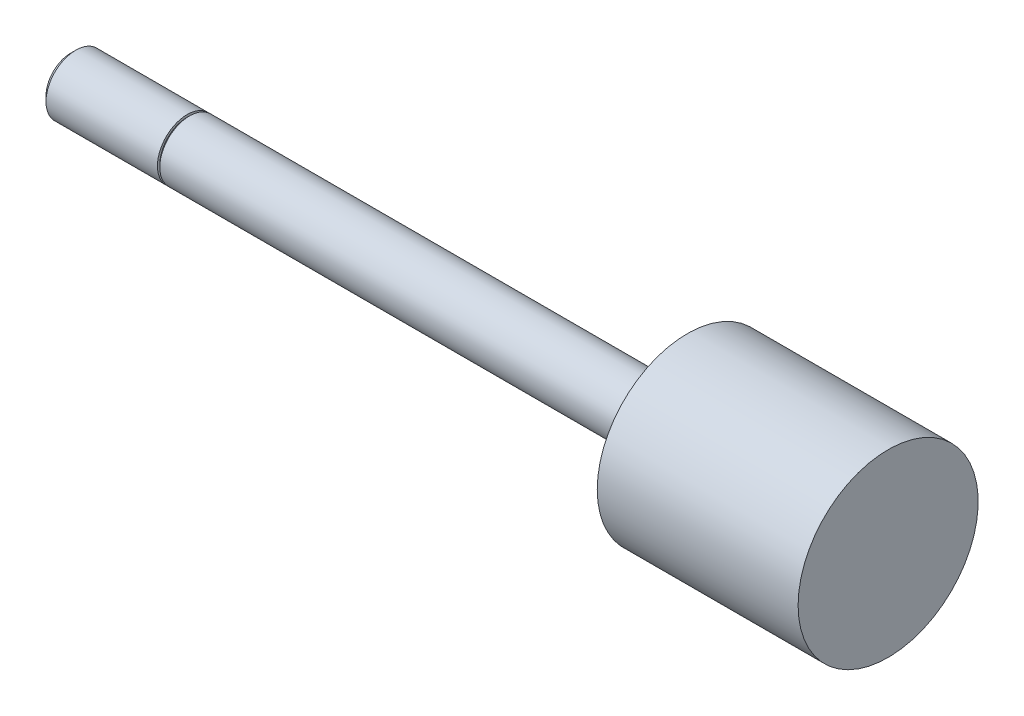
SolidWorks part; units mm, degrees
material "Plain Carbon Steel"
ref_plane "Front Plane" through (0, 0, 0) normal (0, 0, 1) x (1, 0, 0)
ref_plane "Top Plane" through (0, 0, 0) normal (0, 1, 0) x (1, 0, 0)
ref_plane "Right Plane" through (0, 0, 0) normal (1, 0, 0) x (0, 0, -1)
sketch "Sketch1" plane through (0, 0, 0) normal (0, 0, 1) x (1, 0, 0)
  line L0 (0, 0) -> (0, 3.175)
  line L1 (0, 3.175) -> (53.1876, 3.175)
  line L2 (53.1876, 3.175) -> (53.1876, 9.6203)
  line L3 (53.1876, 9.6203) -> (74.6506, 9.6203)
  line L4 (74.6506, 9.6203) -> (74.6506, 0)
  line L5 (74.6506, 0) -> (0, 0)
  line L6 (74.6506, 0) -> (0, 0) construction
revolve "Revolve1" add sketch "Sketch1" angle 360 about L6 reverse direction yes
cosmetic thread "Cosmetic Thread1" parameters "D1"=12.7, "D2"=5.268
sketch "Sketch2" plane through (0, 0, 0) normal (0, 0, 1) x (1, 0, 0)
  line L0 (-12.7, 0) -> (-12.7, 2.634)
  line L1 (-12.7, 2.634) -> (-12.159, 3.175)
  line L2 (-12.159, 3.175) -> (0, 3.175)
  line L3 (0, 3.175) -> (0, 0)
  line L4 (0, 0) -> (-12.7, 0)
  line L5 (0, 0) -> (-12.7, 0) construction
revolve "Revolve2" add sketch "Sketch2" angle 360 about L5 reverse direction yes
ref_plane "Plane1" through (0, 0, 0) normal (1, 0, 0) x (0, 0, -1)
ref_plane "Plane2" through (0, 0, 0) normal (1, 0, 0) x (0, 0, -1)
ref_plane "Plane3" through (127.8382, 0, 0) normal (1, 0, 0) x (0, 0, -1)
ref_plane "Plane4" through (-12.7, 0, 0) normal (1, 0, 0) x (0, 0, -1)
sketch "Sketch3" plane through (0, 0, 0) normal (0, 0, 1) x (1, 0, 0)
  line L0 (-0.254, 2.921) -> (0, 2.921)
  line L1 (0, 2.921) -> (0, 3.429)
  line L2 (0, 3.429) -> (-0.254, 3.429)
  line L3 (-0.254, 3.429) -> (-0.254, 2.921)
  line L4 (0, 0) -> (-0.254, 0) construction
revolve "Cut-Revolve1" cut sketch "Sketch3" angle 360 about L4 reverse direction yes
ref_plane "Plane5" through (0, 0, 0) normal (1, 0, 0) x (0, 0, -1)
ref_plane "Plane6" through (0, 0, 0) normal (1, 0, 0) x (0, 0, -1)
ref_plane "Plane7" through (-16.764, 0, 0) normal (1, 0, 0) x (0, 0, -1)
ref_plane "dia1 XY" through (0, 0, 0) normal (1, 0, 0) x (0, 0, -1)
ref_plane "dia1 XZ" through (0, 3.175, 0) normal (0, -1, 0) x (-1, 0, 0)
ref_plane "dia1 YZ" through (0, 0, 0) normal (0, 0, -1) x (-1, 0, 0)
ref_axis "dia1 X" through (0, 3.175, 80.9) along (0, 0, -1)
ref_axis "dia1 Y" through (0, -50, 0) along (0, 1, 0)
ref_axis "dia1 Z" through (80.9, 3.175, 0) along (-1, 0, 0)
sketch3d "dia1"
  point P0 (0, 3.175, 0)
ref_plane "dia12 XY" through (0, 0, 0) normal (1, 0, 0) x (0, 0, -1)
ref_plane "dia12 XZ" through (0, 0, 0) normal (0, -1, 0) x (-1, 0, 0)
ref_plane "dia12 YZ" through (0, 0, 10.9537) normal (0, 0, -1) x (-1, 0, 0)
ref_axis "dia12 X" through (0, 0, 80.9) along (0, 0, -1)
ref_axis "dia12 Y" through (0, -50, 10.9537) along (0, 1, 0)
ref_axis "dia12 Z" through (80.9, 0, 10.9537) along (-1, 0, 0)
sketch3d "dia12"
  point P0 (0, 0, 10.9537)
ref_plane "dia1r XY" through (0, 0, 0) normal (1, 0, 0) x (0, 0, -1)
ref_plane "dia1r XZ" through (0, 0, 0) normal (0, -1, 0) x (-1, 0, 0)
ref_plane "dia1r YZ" through (0, 0, 10.2235) normal (0, 0, -1) x (-1, 0, 0)
ref_axis "dia1r X" through (0, 0, 80.9) along (0, 0, -1)
ref_axis "dia1r Y" through (0, -50, 10.2235) along (0, 1, 0)
ref_axis "dia1r Z" through (80.9, 0, 10.2235) along (-1, 0, 0)
sketch3d "dia1r"
  point P0 (0, 0, 10.2235)
ref_plane "dia2 XY" through (0, 0, 0) normal (1, 0, 0) x (0, 0, -1)
ref_plane "dia2 XZ" through (0, -3.175, 0) normal (0, -1, 0) x (-1, 0, 0)
ref_plane "dia2 YZ" through (0, 0, 0) normal (0, 0, -1) x (-1, 0, 0)
ref_axis "dia2 X" through (0, -3.175, 80.9) along (0, 0, -1)
ref_axis "dia2 Y" through (0, -50, 0) along (0, 1, 0)
ref_axis "dia2 Z" through (80.9, -3.175, 0) along (-1, 0, 0)
sketch3d "dia2"
  point P0 (0, -3.175, 0)
ref_plane "dia22 XY" through (0, 0, 0) normal (1, 0, 0) x (0, 0, -1)
ref_plane "dia22 XZ" through (0, 0, 0) normal (0, -1, 0) x (-1, 0, 0)
ref_plane "dia22 YZ" through (0, 0, -10.9537) normal (0, 0, -1) x (-1, 0, 0)
ref_axis "dia22 X" through (0, 0, 80.9) along (0, 0, -1)
ref_axis "dia22 Y" through (0, -50, -10.9537) along (0, 1, 0)
ref_axis "dia22 Z" through (80.9, 0, -10.9537) along (-1, 0, 0)
sketch3d "dia22"
  point P0 (0, 0, -10.9537)
ref_plane "dia2r XY" through (0, 0, 0) normal (1, 0, 0) x (0, 0, -1)
ref_plane "dia2r XZ" through (0, 0, 0) normal (0, -1, 0) x (-1, 0, 0)
ref_plane "dia2r YZ" through (0, 0, -10.2235) normal (0, 0, -1) x (-1, 0, 0)
ref_axis "dia2r X" through (0, 0, 80.9) along (0, 0, -1)
ref_axis "dia2r Y" through (0, -50, -10.2235) along (0, 1, 0)
ref_axis "dia2r Z" through (80.9, 0, -10.2235) along (-1, 0, 0)
sketch3d "dia2r"
  point P0 (0, 0, -10.2235)
ref_plane "rl1 XY" through (-12.7, 0, 0) normal (1, 0, 0) x (0, 0, -1)
ref_plane "rl1 XZ" through (0, 0, 0) normal (0, -1, 0) x (-1, 0, 0)
ref_plane "rl1 YZ" through (0, 0, 0) normal (0, 0, -1) x (-1, 0, 0)
ref_axis "rl1 X" through (-12.7, 0, 80.9) along (0, 0, -1)
ref_axis "rl1 Y" through (-12.7, -50, 0) along (0, 1, 0)
ref_axis "rl1 Z" through (80.9, 0, 0) along (-1, 0, 0)
sketch3d "rl1"
  point P0 (-12.7, 0, 0)
ref_plane "rl2 XY" through (0, 0, 0) normal (1, 0, 0) x (0, 0, -1)
ref_plane "rl2 XZ" through (0, 0, 0) normal (0, -1, 0) x (-1, 0, 0)
ref_plane "rl2 YZ" through (0, 0, 0) normal (0, 0, -1) x (-1, 0, 0)
ref_axis "rl2 X" through (0, 0, 80.9) along (0, 0, -1)
ref_axis "rl2 Y" through (0, -50, 0) along (0, 1, 0)
ref_axis "rl2 Z" through (80.9, 0, 0) along (-1, 0, 0)
sketch3d "rl2"
  point P0 (0, 0, 0)
ref_plane "rod_cp XY" through (0, 0, 0) normal (1, 0, 0) x (0, 0, -1)
ref_plane "rod_cp XZ" through (0, 0, 0) normal (0, -1, 0) x (-1, 0, 0)
ref_plane "rod_cp YZ" through (0, 0, 0) normal (0, 0, -1) x (-1, 0, 0)
ref_axis "rod_cp X" through (0, 0, 80.9) along (0, 0, -1)
ref_axis "rod_cp Y" through (0, -50, 0) along (0, 1, 0)
ref_axis "rod_cp Z" through (80.9, 0, 0) along (-1, 0, 0)
sketch3d "rod_cp"
  point P0 (0, 0, 0)
ref_plane "thd1 XY" through (-12.7, 0, 0) normal (1, 0, 0) x (0, 0, -1)
ref_plane "thd1 XZ" through (0, 3.175, 0) normal (0, -1, 0) x (-1, 0, 0)
ref_plane "thd1 YZ" through (0, 0, 0) normal (0, 0, -1) x (-1, 0, 0)
ref_axis "thd1 X" through (-12.7, 3.175, 80.9) along (0, 0, -1)
ref_axis "thd1 Y" through (-12.7, -50, 0) along (0, 1, 0)
ref_axis "thd1 Z" through (80.9, 3.175, 0) along (-1, 0, 0)
sketch3d "thd1"
  point P0 (-12.7, 3.175, 0)
ref_plane "thd2 XY" through (-12.7, 0, 0) normal (1, 0, 0) x (0, 0, -1)
ref_plane "thd2 XZ" through (0, -3.175, 0) normal (0, -1, 0) x (-1, 0, 0)
ref_plane "thd2 YZ" through (0, 0, 0) normal (0, 0, -1) x (-1, 0, 0)
ref_axis "thd2 X" through (-12.7, -3.175, 80.9) along (0, 0, -1)
ref_axis "thd2 Y" through (-12.7, -50, 0) along (0, 1, 0)
ref_axis "thd2 Z" through (80.9, -3.175, 0) along (-1, 0, 0)
sketch3d "thd2"
  point P0 (-12.7, -3.175, 0)
ref_plane "to_rod_clevis XY" through (-16.764, 0, 0) normal (1, 0, 0) x (0, 0, -1)
ref_plane "to_rod_clevis XZ" through (0, 0, 0) normal (0, -1, 0) x (-1, 0, 0)
ref_plane "to_rod_clevis YZ" through (0, 0, 0) normal (0, 0, -1) x (-1, 0, 0)
ref_axis "to_rod_clevis X" through (-16.764, 0, 80.9) along (0, 0, -1)
ref_axis "to_rod_clevis Y" through (-16.764, -50, 0) along (0, 1, 0)
ref_axis "to_rod_clevis Z" through (80.9, 0, 0) along (-1, 0, 0)
sketch3d "to_rod_clevis"
  point P0 (-16.764, 0, 0)
